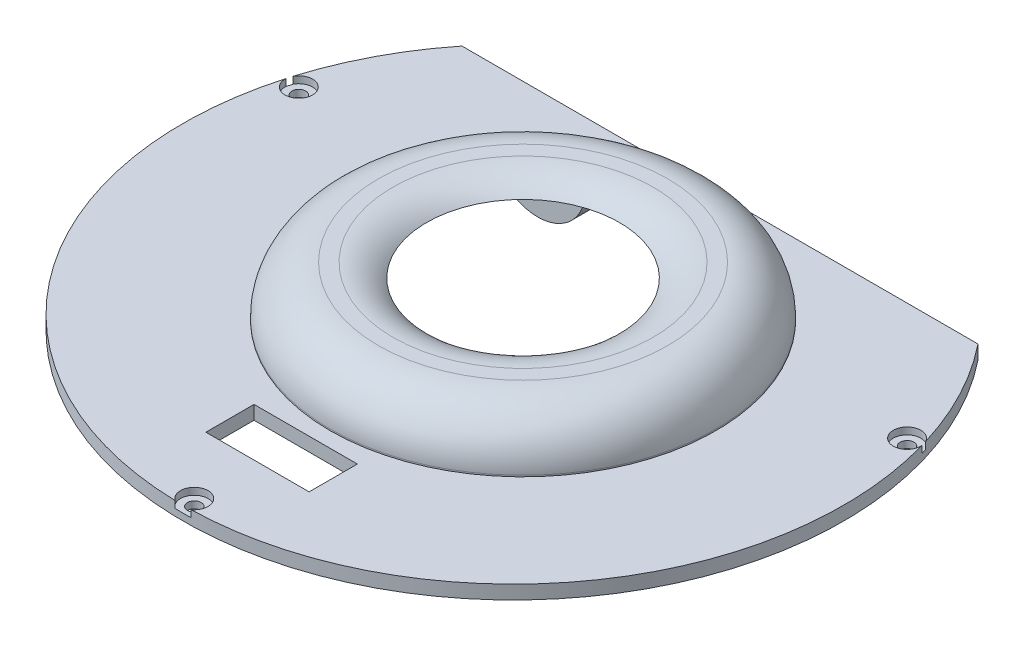
SolidWorks part; units mm, degrees
ref_plane "Front Plane" through (0, 0, 0) normal (0, 0, 1) x (1, 0, 0)
ref_plane "Top Plane" through (0, 0, 0) normal (0, 1, 0) x (1, 0, 0)
ref_plane "Right Plane" through (0, 0, 0) normal (1, 0, 0) x (0, 0, -1)
sketch "Sketch1" plane through (0, 0, 0) normal (0, 1, 0) x (1, 0, 0)
  line L0 (-37.47, 30) -> (37.47, 30)
  arc A0 (-37.47, 30) -> (37.47, 30) centre (0, 0) ccw
extrude "Boss-Extrude1" add sketch "Sketch1" along normal blind 2
sketch "Sketch2" plane through (0, 2, 0) normal (0, 1, 0) x (1, 0, 0)
  circle A0 centre (1.35, 0.05) radius 5
  dimension "D1" = 10
sketch "Sketch4" plane through (0, 2, 0) normal (0, 1, 0) x (1, 0, 0)
  circle A0 centre (-44.167, 13) radius 1
  circle A1 centre (0, -46.3478) radius 1
  circle A2 centre (44.167, 13) radius 1
extrude "Cut-Extrude3" cut sketch "Sketch4" against normal blind 2
sketch "Sketch5" plane through (0, 2, 0) normal (0, 1, 0) x (1, 0, 0)
  circle A0 centre (-44.167, 13) radius 2
  circle A1 centre (0, -46.3478) radius 2
  circle A2 centre (44.167, 13) radius 2
  dimension "D1" = 4
  dimension "D2" = 4
  dimension "D3" = 4
extrude "Cut-Extrude4" cut sketch "Sketch5" against normal blind 1
extrude "Cut-Extrude1" cut sketch "Sketch2" against normal blind 10
sketch "Sketch3" plane through (0, 2, 0) normal (0, 1, 0) x (1, 0, 0)
  circle A0 centre (1.35, 0.05) radius 24
  dimension "D1" = 48
extrude "Cut-Extrude2" cut sketch "Sketch3" against normal blind 10
sketch "Sketch6" plane through (0, 2, 0) normal (0, 1, 0) x (1, 0, 0)
  circle A0 centre (1.35, 0.05) radius 24
  circle A1 centre (1.35, 0.05) radius 28
  dimension "D1" = 48
  dimension "D2" = 4
extrude "Boss-Extrude2" add sketch "Sketch6" along normal blind 7.2
sketch "Sketch7" plane through (0, 9.2, 0) normal (0, 1, 0) x (1, 0, 0)
  circle A0 centre (1.35, 0.05) radius 28
  circle A1 centre (1.35, 0.05) radius 14
  dimension "D1" = 56
  dimension "D2" = 14
extrude "Boss-Extrude3" add sketch "Sketch7" against normal blind 2
sketch "Sketch8" plane through (0, 9.2, 0) normal (0, 1, 0) x (1, 0, 0)
  line L0 (1.35, 14.05) -> (1.35, 24.05) construction
  line L1 (11.35, 21.8674) -> (11.35, 9.848)
  line L2 (-8.65, 21.8674) -> (-8.65, 9.848)
  arc A0 (11.35, 9.848) -> (-8.65, 9.848) centre (1.35, 0.05) ccw
  arc A1 (11.35, 21.8674) -> (-8.65, 21.8674) centre (1.35, 0.05) ccw
  dimension "D1" = 28
  dimension "D2" = 10
  dimension "D3" = 20
  dimension "D4" = 10
sketch "Sketch9" plane through (0, 0, -30) normal (0, 0, -1) x (-1, 0, 0)
  line L0 (-37.47, 2) -> (37.47, 2) construction
  line L1 (-29.47, 2) -> (-15.47, 2)
  line L2 (-29.47, 2) -> (-29.47, -10)
  line L3 (-29.47, -10) -> (-15.47, -10)
  line L4 (-15.47, 2) -> (-15.47, -10)
  line L5 (-37.47, 2) -> (-37.47, 0) construction
  line L6 (15.47, 2) -> (29.47, 2)
  line L7 (15.47, 2) -> (15.47, -10)
  line L8 (15.47, -10) -> (29.47, -10)
  line L9 (29.47, 2) -> (29.47, -10)
  line L10 (37.47, 2) -> (37.47, 0) construction
  dimension "D1" = 14
  dimension "D2" = 14
  dimension "D3" = 8
  dimension "D4" = 8
  dimension "D5" = 12
  dimension "D6" = 12
extrude "Boss-Extrude4" add sketch "Sketch9" against normal blind 4
fillet "Fillet1" radius 7 4 edges at (-29.47, -10, -28) (-15.47, -10, -28) (15.47, -10, -28) (29.47, -10, -28)
sketch "Sketch10" plane through (0, 0, -30) normal (0, 0, -1) x (-1, 0, 0)
  circle A0 centre (-22.47, -3) radius 3.25
  circle A1 centre (22.47, -3) radius 3.25
  dimension "D1" = 6.5
  dimension "D2" = 6.5
extrude "Cut-Extrude6" cut sketch "Sketch10" against normal blind 3
sketch "Sketch11" plane through (0, 9.2, 0) normal (0, 1, 0) x (1, 0, 0)
  line L2 (-8.65, 15.0166) -> (-8.65, 9.848)
  line L4 (11.35, 15.0166) -> (11.35, 9.848)
  arc A0 (11.35, 9.848) -> (-8.65, 9.848) centre (1.35, 0.05) ccw
  arc A1 (11.35, 15.0166) -> (-8.65, 15.0166) centre (1.35, 0.05) ccw
  dimension "D1" = 28
  dimension "D2" = 4
extrude "Boss-Extrude5" add sketch "Sketch11" against normal blind 2
fillet "Fillet2" radius 7 1 edges at (1.35, 9.2, 27.95)
fillet "Fillet3" radius 7 1 edges at (1.35, 9.2, 13.95)
fillet "Fillet4" radius 4 1 edges at (1.35, 7.2, 23.95)
fillet "Fillet5" radius 4 1 edges at (1.35, 0, 23.95)
sketch "Sketch12" plane through (0, 2, 0) normal (0, 1, 0) x (1, 0, 0)
  line L0 (0, -52.4131) -> (0, 9.7302) construction
  line L2 (-7.5, -30.1664) -> (7.5, -30.1664)
  line L3 (-7.5, -30.1664) -> (-7.5, -37.1664)
  line L4 (-7.5, -37.1664) -> (7.5, -37.1664)
  line L5 (7.5, -30.1664) -> (7.5, -37.1664)
  point P7 (0, -37.1664)
  dimension "D1" = 15
  dimension "D2" = 7
extrude "Cut-Extrude7" cut sketch "Sketch12" against normal blind 10
